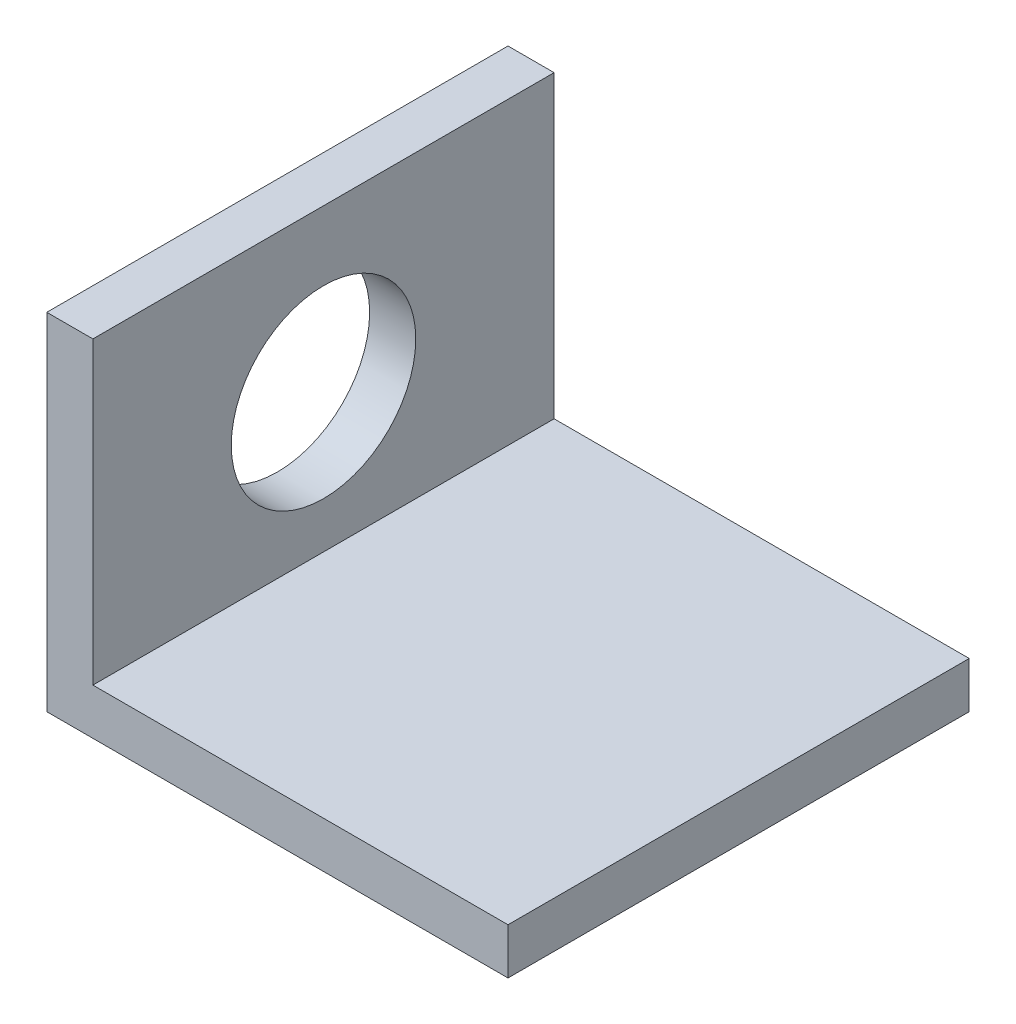
SolidWorks part; units mm, degrees
ref_plane "Ebene vorne" through (0, 0, 0) normal (0, 0, 1) x (1, 0, 0)
ref_plane "Ebene oben" through (0, 0, 0) normal (0, 1, 0) x (1, 0, 0)
ref_plane "Ebene rechts" through (0, 0, 0) normal (1, 0, 0) x (0, 0, -1)
sketch "Skizze1" plane through (0, 0, 0) normal (0, 0, 1) x (1, 0, 0)
  line L0 (0, 0) -> (0, 6.5)
  line L1 (0, 6.5) -> (-1, 6.5)
  line L2 (-1, 6.5) -> (-1, -1)
  line L3 (-1, -1) -> (9, -1)
  line L4 (9, -1) -> (9, 0)
  line L5 (9, 0) -> (0, 0)
  dimension "D1" = 1
  dimension "D2" = 1
  dimension "D3" = 7.5
  dimension "D4" = 10
extrude "Aufsatz-Linear austragen1" add sketch "Skizze1" along normal blind 10
sketch "Skizze2" plane through (-1, 0, 0) normal (-1, 0, 0) x (0, 0, 1)
  line L0 (10, 6.5) -> (0, 6.5) construction
  circle A0 centre (5, 3) radius 2
  point P6 (5, 6.5)
  dimension "D1" = 4
  dimension "D2" = 3.5
extrude "Schnitt-Linear austragen1" cut sketch "Skizze2" against normal through all
ref_axis "ASS_Optical_Axis" through (0, 3, 5) along (-1, 0, 0)
ref_point "Punkt1"
sketch "Skizze3" plane through (0, 0, 0) normal (1, 0, 0) x (0, 0, -1)
  line L0 (-5, 3) -> (-2.8349, 1.75)
  line L1 (-5, 3) -> (-5, 5.5)
  line L2 (-5, 3) -> (-7.1651, 1.75)
  line L3 (-10, 0) -> (-10, 6.5) construction
  dimension "D1" = 120
  dimension "D2" = 120
  dimension "D3" = 2.5
